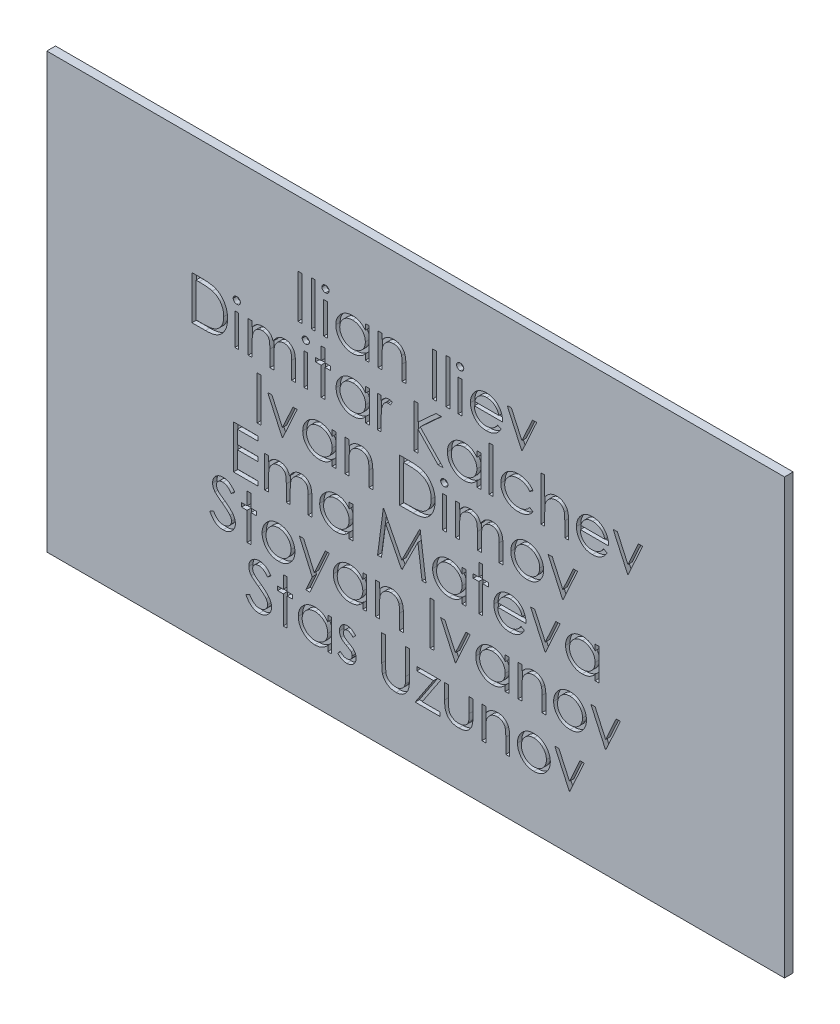
SolidWorks part; units mm, degrees
ref_plane "Front Plane" through (0, 0, 0) normal (0, 0, 1) x (1, 0, 0)
ref_plane "Top Plane" through (0, 0, 0) normal (0, 1, 0) x (1, 0, 0)
ref_plane "Right Plane" through (0, 0, 0) normal (1, 0, 0) x (0, 0, -1)
sketch "Sketch2" plane through (0, 0, 0) normal (0, 0, 1) x (1, 0, 0)
  line L1 (425, -250) -> (-425, -250)
  line L2 (425, -250) -> (425, 250)
  line L3 (425, 250) -> (-425, 250)
  line L4 (-425, -250) -> (-425, 250)
  line L5 (425, -250) -> (-425, 250) construction
  line L6 (425, 250) -> (-425, -250) construction
  point P0 (0, 0)
  dimension "D1" = 500
  dimension "D2" = 850
extrude "Boss-Extrude1" add sketch "Sketch2" along normal blind 10
sketch "Sketch3" plane through (0, 0, 0) normal (0, 0, -1) x (-1, 0, 0)
  line L1 (350, -175) -> (-350, -175) construction
  line L2 (350, -175) -> (350, 175) construction
  line L3 (350, 175) -> (-350, 175) construction
  line L4 (-350, -175) -> (-350, 175) construction
  line L5 (350, -175) -> (-350, 175) construction
  line L6 (350, 175) -> (-350, -175) construction
  line L7 (425, 250) -> (425, -250) construction
  circle A0 centre (-350, 175) radius 20
  circle A1 centre (350, 175) radius 20
  circle A2 centre (350, -175) radius 20
  circle A3 centre (-350, -175) radius 20
  point P0 (0, 0)
  dimension "D4" = 40
  dimension "D5" = 40
  dimension "D6" = 40
  dimension "D7" = 40
  dimension "D1" = 350
  dimension "D2" = 700
  dimension "D3" = 75
extrude "Boss-Extrude2" add sketch "Sketch3" along normal blind 30
sketch "Sketch5" plane through (0, 0, 10) normal (0, 0, 1) x (1, 0, 0)
  line L0 (-425, 187.5) -> (425, 187.5) construction
  line L1 (-425, 250) -> (-425, -250) construction
  line L2 (425, -250) -> (425, 250) construction
  line L3 (425, 250) -> (-425, 250) construction
  line L4 (-425, 125) -> (425, 125) construction
  line L5 (-425, -250) -> (425, -250) construction
  line L6 (425, 62.5) -> (-425, 62.5) construction
  line L8 (-425, 0) -> (425, 0) construction
  line L10 (425, -62.5) -> (-425, -62.5) construction
  line L12 (-425, -125) -> (425, -125) construction
  line L14 (425, -187.5) -> (-425, -187.5) construction
  text T0 "Ilian Iliev" font "Century Gothic" height 50
  text T1 "Dimitar Kalchev" font "Century Gothic" height 50
  text T2 "Ivan Dimov" font "Century Gothic" height 50
  text T3 "Ema Mateva" font "Century Gothic" height 50
  text T4 "Stoyan Ivanov" font "Century Gothic" height 50
  text T5 "Stas Uzunov" font "Century Gothic" height 50
  dimension "D1" = 62.5
  dimension "D2" = 62.5
  dimension "D3" = 62.5
  dimension "D4" = 62.5
  dimension "D5" = 62.5
  dimension "D6" = 62.5
  dimension "D7" = 62.5
  dimension "D8" = 62.5
extrude "Cut-Extrude2" cut sketch "Sketch5" against normal blind 5
